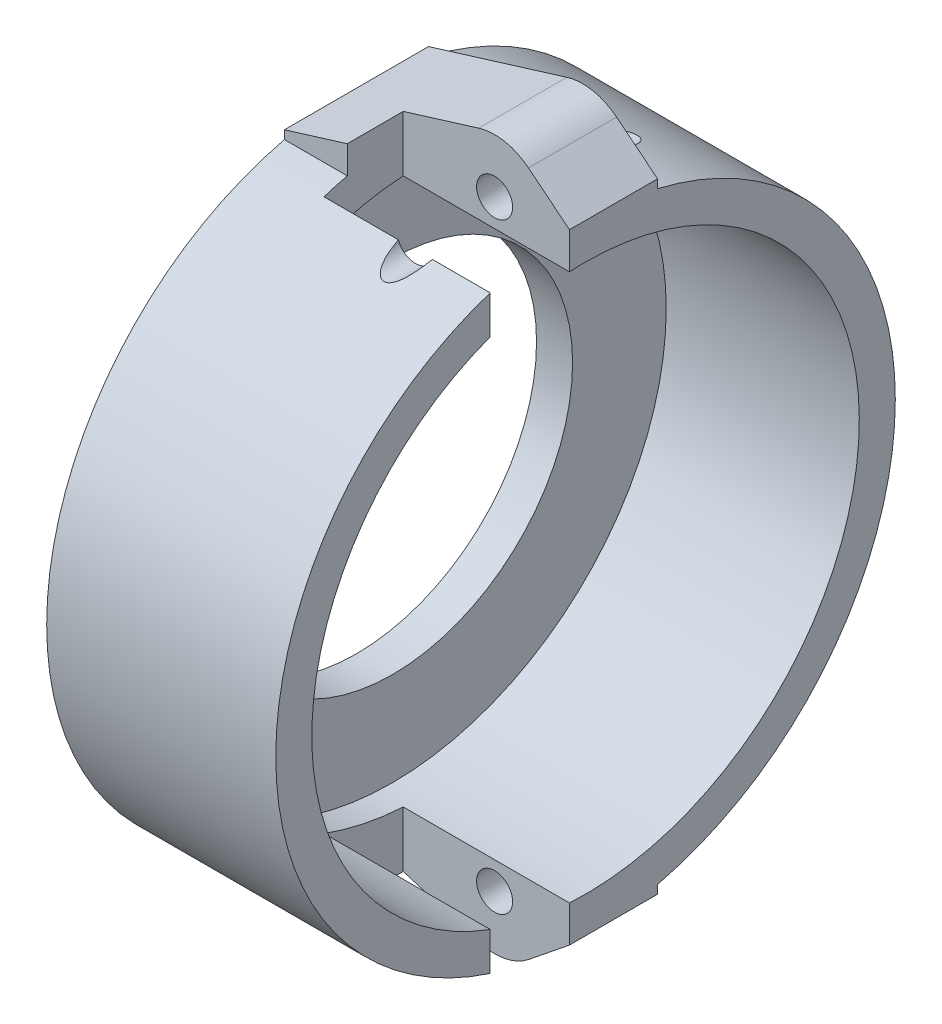
SolidWorks part; units mm, degrees
ref_plane "Front Plane" through (0, 0, 0) normal (0, 0, 1) x (1, 0, 0)
ref_plane "Top Plane" through (0, 0, 0) normal (0, 1, 0) x (1, 0, 0)
ref_plane "Right Plane" through (0, 0, 0) normal (1, 0, 0) x (0, 0, -1)
sketch "Sketch1" plane through (0, 0, 0) normal (0, 0, 1) x (1, 0, 0)
  line L2 (5, -38) -> (5, -25)
  line L4 (5, -25) -> (0, -25)
  line L5 (0, -25) -> (0, -43)
  line L6 (0, -43) -> (31.8, -43)
  line L7 (31.8, -38) -> (31.8, -43)
  line L8 (31.8, -38) -> (5, -38)
  line L9 (96.0175, 0) -> (-96.0175, 0) construction
  dimension "D1" = 5
  dimension "D2" = 5
  dimension "D3" = 26.8
  dimension "D4" = 18
  dimension "D5" = 25
revolve "Revolve1" add sketch "Sketch1" angle 360 about L9
ref_axis "Axis1" through (33.39, 0, 0) along (-1, 0, 0)
ref_plane "Plane4" through (0, -50, 0) normal (0, 1, 0) x (1, 0, 0)
sketch "Sketch3" plane through (0, 0, 0) normal (0, 0, 1) x (1, 0, 0)
  line L0 (31.8, -43) -> (26.1144, -47.5815)
  line L1 (0, -43) -> (19.2024, -48.9098)
  line L4 (31.8, -43) -> (31.8, 43) construction
  line L5 (31.8, -43) -> (31.8, -38)
  line L10 (31.8, -38) -> (0, -38)
  line L11 (0, -43) -> (0, -38)
  arc A0 (19.2024, -48.9098) -> (26.1144, -47.5815) centre (21.4085, -41.7416) ccw
  dimension "D1" = 15
extrude "Boss-Extrude1" add sketch "Sketch3" along normal mid plane 20
sketch "Sketch4" plane through (0, 0, 0) normal (0, 0, 1) x (1, 0, 0)
  circle A0 centre (21.4085, -41.7416) radius 2.5 construction
  circle A1 centre (21.4085, -41.7416) radius 2.5
extrude "Cut-Extrude1" cut sketch "Sketch4" against normal through all and the other way through all
sketch "Sketch5" plane through (0, -50, 0) normal (0, 1, 0) x (1, 0, 0)
  line L8 (20.8778, -13.2314) -> (121.9639, -13.2314)
  line L9 (20.8778, -2.2314) -> (20.8778, -13.2314)
  line L10 (121.9639, -2.2314) -> (20.8778, -2.2314)
  line L11 (121.9639, -13.2314) -> (121.9639, -2.2314)
  line L12 (8.7257, -13.2314) -> (31.8, -13.2314)
  line L13 (8.7257, -2.2314) -> (8.7257, -13.2314)
  line L14 (31.8, -2.2314) -> (8.7257, -2.2314)
  line L15 (31.8, -13.2314) -> (31.8, -2.2314)
  line L28 (31.8, -43) -> (31.8, 43) construction
  dimension "D1" = 0.5
extrude "Cut-Extrude2" cut sketch "Sketch5" along normal up to surface (12.0656 mm away) up to face at (5, 38, 0)
mirror "Mirror1" about plane through (0, 0, 0) normal (0, 1, 0) of "Cut-Extrude2", "Cut-Extrude1", "Boss-Extrude1"
